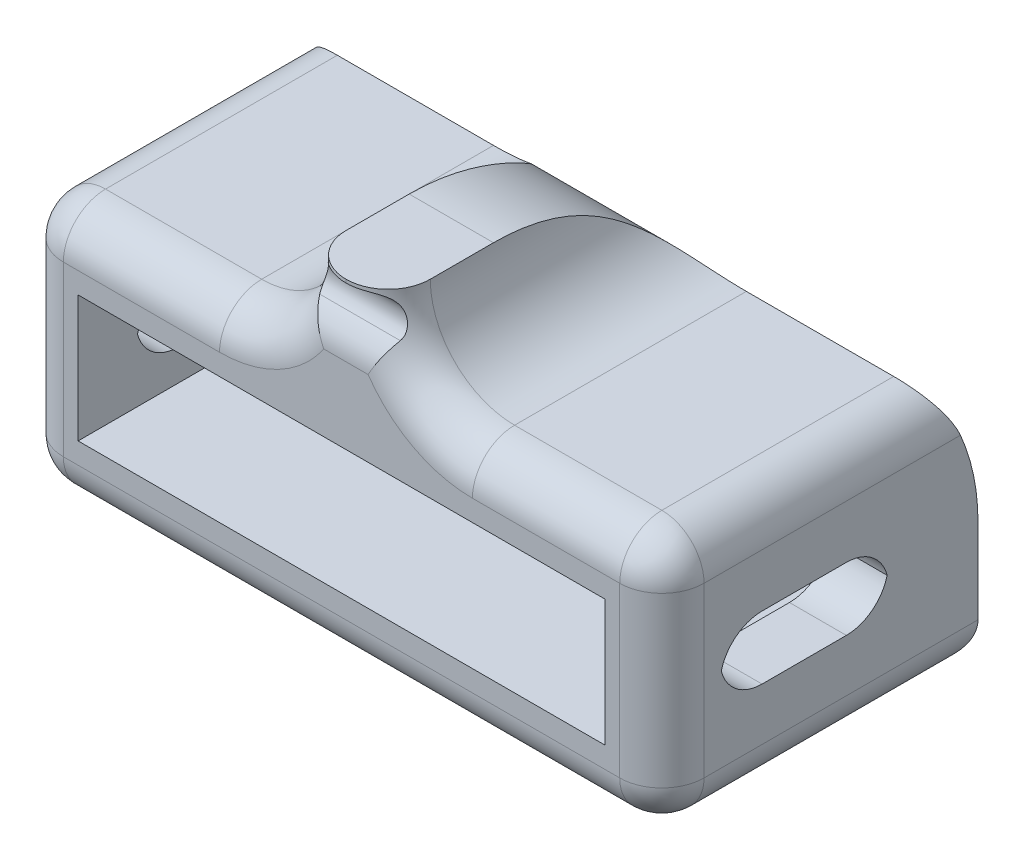
SolidWorks part; units mm, degrees
ref_plane "Front Plane" through (0, 0, 0) normal (0, 0, 1) x (1, 0, 0)
ref_plane "Top Plane" through (0, 0, 0) normal (0, 1, 0) x (1, 0, 0)
ref_plane "Right Plane" through (0, 0, 0) normal (1, 0, 0) x (0, 0, -1)
sketch "Sketch1" plane through (0, 0, 0) normal (0, 1, 0) x (1, 0, 0)
  line L1 (-41.6963, 19.6283) -> (-11.2963, 19.6283)
  line L2 (-41.6963, 19.6283) -> (-41.6963, 4.6283)
  line L3 (-41.6963, 4.6283) -> (-11.2963, 4.6283)
  line L4 (-11.2963, 19.6283) -> (-11.2963, 4.6283)
  dimension "D1" = 30.4
  dimension "D2" = 15
extrude "Boss-Extrude1" add sketch "Sketch1" along normal blind 12
sketch "Sketch2" plane through (0, 0, -4.6283) normal (0, 0, 1) x (1, 0, 0)
  line L0 (-41.6963, 12) -> (-11.2963, 12) construction
  line L1 (-38.9963, 9) -> (-13.9963, 9)
  line L2 (-38.9963, 9) -> (-38.9963, 3)
  line L3 (-38.9963, 3) -> (-13.9963, 3)
  line L4 (-13.9963, 9) -> (-13.9963, 3)
  line L5 (-11.2963, 12) -> (-11.2963, 0) construction
  dimension "D1" = 25
  dimension "D2" = 6
  dimension "D3" = 3
  dimension "D4" = 2.7
extrude "Cut-Extrude1" cut sketch "Sketch2" against normal through all
sketch "Sketch3" plane through (0, 12, 0) normal (0, 1, 0) x (1, 0, 0)
  line L0 (-26.0928, 19.0641) -> (-26.4963, 4.6283) construction
  line L1 (-41.6963, 4.6283) -> (-11.2963, 4.6283) construction
  line L2 (-11.2963, 19.6283) -> (-41.6963, 19.6283) construction
  line L3 (-24.2867, 4.6283) -> (-28.2867, 4.6283)
  line L4 (-24.2867, 4.6283) -> (-24.2867, 19.6283)
  line L5 (-24.2867, 19.6283) -> (-28.2867, 19.6283)
  line L6 (-28.2867, 4.6283) -> (-28.2867, 19.6283)
  line L7 (-24.2867, 4.6283) -> (-28.2867, 19.6283) construction
  line L8 (-24.2867, 19.6283) -> (-28.2867, 4.6283) construction
  point P4 (-26.2867, 12.1283)
  dimension "D1" = 15
  dimension "D2" = 4
extrude "Boss-Extrude2" add sketch "Sketch3" along normal blind 4
sketch "Sketch4" plane through (-24.2867, 0, 0) normal (1, 0, 0) x (0, 0, -1)
  line L0 (4.6283, 16) -> (4.6283, 12) construction
  circle A0 centre (4.6283, 14.844) radius 1
extrude "Cut-Extrude2" cut sketch "Sketch4" against normal blind 4
fillet "Fillet1" radius 4 2 edges
fillet "Fillet2" radius 10 1 edges at (-26.2867, 16, -19.6283)
fillet "Fillet5" radius 2 13 edges at (-26.4963, 0, -19.6283) (-41.6963, 0, -12.1283) (-26.4963, 0, -4.6283) (-11.2963, 0, -12.1283) (-41.6963, 12, -11.1283) (-11.2963, 12, -11.1283) (-11.2963, 6, -4.6283) (-41.6963, 6, -4.6283) (-30.3663, 12.4911, -4.6283) (-26.2867, 13.844, -4.6283) (-22.2071, 12.4911, -4.6283)
sketch "Sketch5" plane through (-11.2963, 0, 0) normal (1, 0, 0) x (0, 0, -1)
  line L1 (7.3812, 7.4827) -> (15.3812, 7.4827)
  line L2 (7.3812, 7.4827) -> (7.3812, 4.4827)
  line L3 (7.3812, 4.4827) -> (15.3812, 4.4827)
  line L4 (15.3812, 7.4827) -> (15.3812, 4.4827)
  dimension "D1" = 8
  dimension "D2" = 3
extrude "Cut-Extrude3" cut sketch "Sketch5" against normal through all
fillet "Fillet6" radius 2 8 edges at (-40.3463, 7.4827, -7.3812) (-40.3463, 7.4827, -15.3812) (-40.3463, 4.4827, -15.3812) (-40.3463, 4.4827, -7.3812) (-12.6463, 4.4827, -15.3812) (-12.6463, 7.4827, -15.3812) (-12.6463, 7.4827, -7.3812) (-12.6463, 4.4827, -7.3812)
